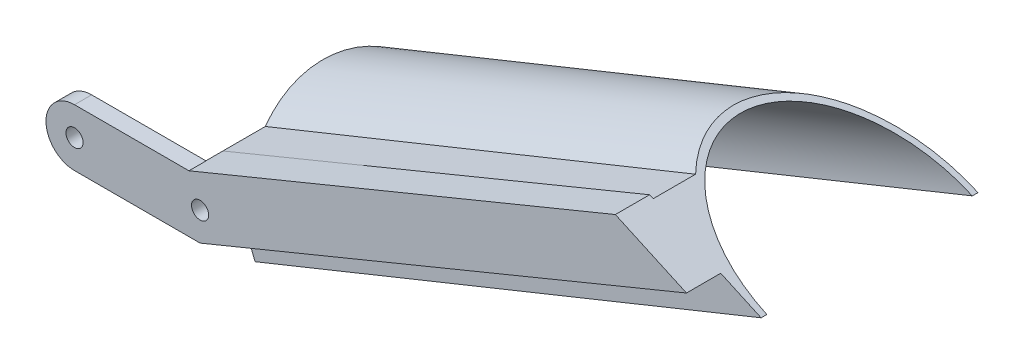
SolidWorks part; units mm, degrees
ref_plane "Front Plane" through (0, 0, 0) normal (0, 0, 1) x (1, 0, 0)
ref_plane "Top Plane" through (0, 0, 0) normal (0, 1, 0) x (1, 0, 0)
ref_plane "Right Plane" through (0, 0, 0) normal (1, 0, 0) x (0, 0, -1)
sketch "Sketch1" plane through (0, 0, 0) normal (0, 0, 1) x (1, 0, 0)
  line L0 (0, 0) -> (22, 0) construction
  line L1 (0, 5) -> (22, 5)
  line L2 (0, -5) -> (22, -5)
  line L3 (21.5213, 1.4216) -> (23.9914, -4.5863) construction
  line L4 (46.409, 15.8375) -> (51.4959, 17.929) construction
  line L5 (20.05, 5) -> (46.409, 15.8375)
  line L6 (51.4959, 17.929) -> (53.6145, 12.7761) construction
  line L7 (53.3599, 12.6714) -> (58.8728, 10.1603)
  line L8 (46.409, 15.8375) -> (53.3599, 12.6714)
  line L9 (48.359, 5.8375) -> (58.8728, 10.1603)
  line L11 (48.359, 5.8375) -> (22, -5)
  arc A0 (0, 5) -> (0, -5) centre (0, 0) ccw
  arc A1 (22, -5) -> (22, 5) centre (22, 0) ccw
  circle A2 centre (0, 0) radius 1.5
  circle A3 centre (22, 0) radius 1.5
  point P3 (11, 0)
  dimension "D2" = 10
  dimension "D11" = 3
  dimension "D1" = 22
  dimension "D3" = 157.65
  dimension "D4" = 1.95
  dimension "D5" = 34
  dimension "D9" = 5.5
extrude "Boss-Extrude1" add sketch "Sketch1" along normal blind 3 contours A1 L1 A0 L2 A3 A2 | A1 L8 L1 region at (10.9566, 0.015, 0) region at (39.2383, 7.2413, 0)
sketch "草图1" plane through (0, 0, 3) normal (0, 0, 1) x (1, 0, 0)
  line L5 (46.409, 15.8375) -> (58.8728, 10.1603)
  line L7 (98.5446, 37.273) -> (111.0084, 31.5958)
  line L8 (46.409, 15.8375) -> (98.5446, 37.273)
  line L17 (58.8728, 10.1603) -> (111.0084, 31.5958)
extrude "凸台-拉伸1" add sketch "草图1" against normal up to surface (3 mm away) up to face at (23.5, 0, 0)
sketch "草图2" plane through (0, 0, 0) normal (0, 0, -1) x (-1, 0, 0)
  line L0 (-22, 0) -> (0, 0)
  line L1 (0, 0) -> (-6.7184, -16.6453)
  line L2 (-6.7184, -16.6453) -> (-25.6368, -9.0032)
  circle A0 centre (-22, 0) radius 9.71
  circle A1 centre (0, 0) radius 17.95
ref_plane "基准面1" through (6.7231, -16.6434, 0) normal (-0.3745, 0.9272, 0) x (0.9272, 0.3745, 0)
sketch "草图3" plane through (0, 0, 0) normal (0, 0, -1) x (-1, 0, 0)
  line L0 (-22, 0) -> (-27.5784, -13.8097)
ref_plane "基准面2" through (18.9137, 7.6402, 0) normal (-0.9272, -0.3745, 0) x (0.3745, -0.9272, 0)
ref_plane "基准面3" through (0, 0, 3) normal (0, 0, 1) x (1, 0, 0)
ref_axis "基准轴1" through (29.9958, -19.794, 3) along (-0.3745, 0.9272, 0)
ref_axis "基准轴2" through (116.8088, 27.8257, 3) along (-0.9272, -0.3745, 0)
ref_point "点1"
sketch "草图4" plane through (0, 0, 0) normal (0, 0, -1) x (-1, 0, 0)
  line L0 (-111.0084, 31.5958) -> (-98.5446, 37.273)
  line L1 (-111.0084, 31.5958) -> (-23.7321, -4.2879)
  line L2 (-98.5446, 37.273) -> (-19.9902, 4.9754)
  line L4 (-19.9902, 4.9754) -> (-21.0636, 2.318)
  line L6 (-22.9364, -2.318) -> (-23.7321, -4.2879)
  arc A0 (-21.0636, 2.318) -> (-22.9364, -2.318) centre (-22, 0) ccw
extrude "凸台-拉伸2" add sketch "草图4" along normal blind 3
sketch "草图5" plane through (18.9137, 7.6402, 0) normal (-0.9272, -0.3745, 0) x (0.3745, -0.9272, 0)
  line L0 (17.95, -3) -> (17.95, -4)
  line L1 (17.95, -41) -> (17.95, -40)
  line L2 (17.95, -3) -> (2.874, -3)
  line L3 (2.874, -3) -> (2.874, -10.4365)
  arc A0 (17.95, -4) -> (17.95, -40) centre (17.95, -22) ccw
  arc A1 (2.874, -10.4365) -> (17.95, -41) centre (17.95, -22) ccw
extrude "凸台-拉伸3" add sketch "草图5" against normal up to surface (99.745 mm away) up to face at (104.7765, 34.4344, 0)
sketch "草图6" plane through (0, 0, 0) normal (0, 0, -1) x (-1, 0, 0)
  line L0 (-118.1213, 28.3558) -> (-94.2786, 39.2162)
  line L1 (-118.1213, 28.3558) -> (-114.3105, 26.8165)
  line L2 (-94.2786, 39.2162) -> (-90.4677, 37.6768)
  line L3 (-114.3105, 26.8165) -> (-90.4677, 37.6768)
  line L4 (-18.5205, 8.6138) -> (-94.2786, 39.2162) construction
  dimension "D1" = 4.11
extrude "切除-拉伸1" cut sketch "草图6" against normal mid plane 90
